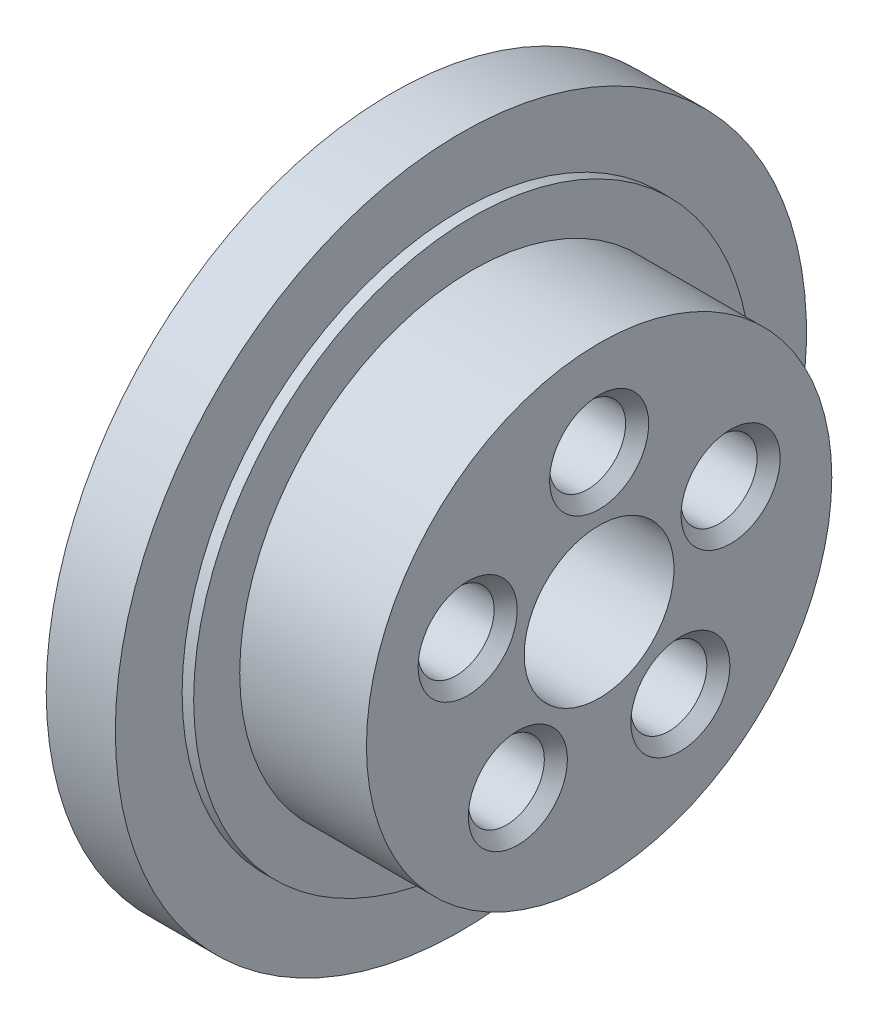
SolidWorks part; units mm, degrees
ref_plane "Front Plane" through (0, 0, 0) normal (0, 0, 1) x (1, 0, 0)
ref_plane "Top Plane" through (0, 0, 0) normal (0, 1, 0) x (1, 0, 0)
ref_plane "Right Plane" through (0, 0, 0) normal (1, 0, 0) x (0, 0, -1)
sketch "Sketch1" plane through (0, 0, 0) normal (0, 0, 1) x (1, 0, 0)
  line L0 (0, 30) -> (6, 30)
  line L9 (6, 30) -> (6, 24.2)
  line L10 (6, 24.2) -> (7, 24.2)
  line L11 (7, 24.2) -> (7, 20.2)
  line L12 (7, 20.2) -> (18, 20.2)
  line L13 (18, 20.2) -> (18, 6.5)
  line L14 (18, 6.5) -> (6, 6.5)
  line L15 (6, 6.5) -> (6, 7.5)
  line L16 (6, 7.5) -> (0, 7.5)
  line L17 (0, 7.5) -> (0, 30)
  line L18 (0, 0) -> (18, 0) construction
  dimension "D1" = 6
  dimension "D2" = 12
  dimension "D3" = 1
  dimension "D4" = 6
  dimension "D5" = 4
  dimension "D6" = 7.5
  dimension "D7" = 30
  dimension "D8" = 13.7
  dimension "D9" = 6.5
revolve "Revolve1" add sketch "Sketch1" angle 360 about L18
sketch "Sketch2" plane through (0, 0, 0) normal (-1, 0, 0) x (0, 0, 1)
  circle A0 centre (0, 0) radius 20 construction
  circle A1 centre (0, 20) radius 2.5
  circle A2 centre (17.3205, 10) radius 2.5
  circle A3 centre (17.3205, -10) radius 2.5
  circle A4 centre (0, -20) radius 2.5
  circle A5 centre (-17.3205, -10) radius 2.5
  circle A6 centre (-17.3205, 10) radius 2.5
  point P18 (0, 0)
  dimension "D1" = 40
  dimension "D2" = 5
extrude "Cut-Extrude1" cut sketch "Sketch2" against normal blind 4.5
sketch "Sketch3" plane through (18, 0, 0) normal (1, 0, 0) x (0, 0, -1)
  circle A0 centre (0, 0) radius 12 construction
  circle A3 centre (0, 12) radius 3.3
  circle A6 centre (11.4127, 3.7082) radius 3.3
  circle A7 centre (7.0534, -9.7082) radius 3.3
  circle A8 centre (-7.0534, -9.7082) radius 3.3
  circle A9 centre (-11.4127, 3.7082) radius 3.3
  point P15 (0, 0)
  dimension "D1" = 24
  dimension "D2" = 6.6
extrude "Cut-Extrude2" cut sketch "Sketch3" against normal blind 10.5
chamfer "Chamfer1" distance 1 angle 45 5 edges at (18, 3.7082, 8.1127) (18, -9.7082, 3.7534) (18, -9.7082, -10.3534) (18, 3.7082, -14.7127) (18, 12, -3.3)
sketch "Sketch4" plane through (0, 0, 0) normal (-1, 0, 0) x (0, 0, 1)
  circle A0 centre (0, 0) radius 10
  dimension "D1" = 20
extrude "Cut-Extrude3" cut sketch "Sketch4" against normal offset from surface (2 mm away) 4 contours A0 up to face at (6, 0, 6.5)
equation "\"R_ROLL\"= 5mm"
equation "\"D_SUN\"= 80mm"
equation "\"NUM_ROLL\"= 16"
equation "\"RHO\"= 1mm"
equation "\"D_SHAFT\"= 15mm"
equation "\"D_OUTPUT\"= 40mm"
equation "\"NUM_OUT\"= 6"
equation "\"R_OUT_ROLL\"= 5mm"
equation "\"D1@Sketch2\"=\"D_OUTPUT\""
